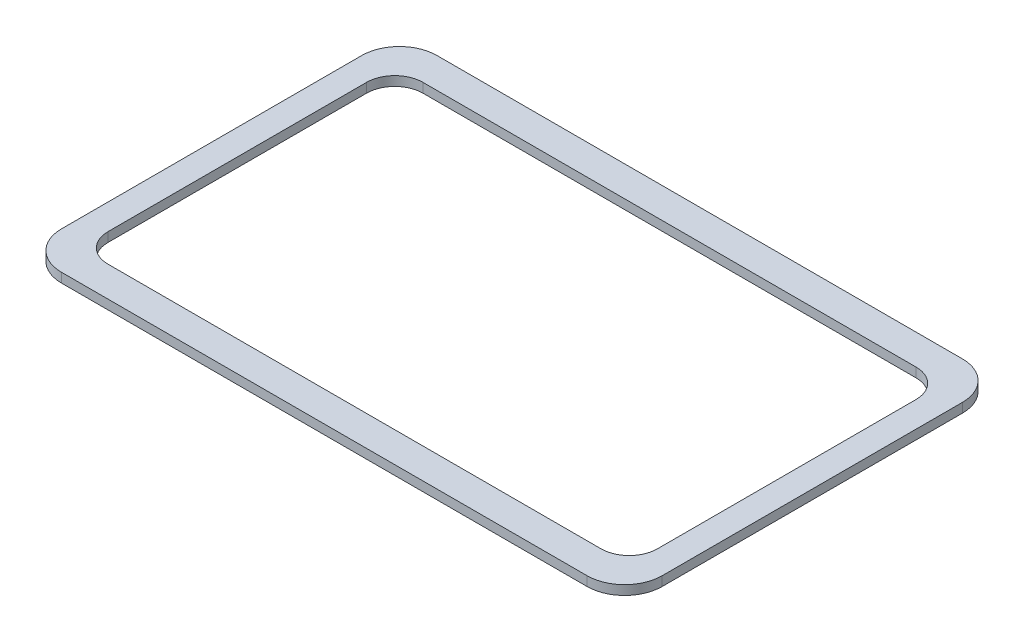
SolidWorks part; units mm, degrees
ref_plane "Front Plane" through (0, 0, 0) normal (0, 0, 1) x (1, 0, 0)
ref_plane "Top Plane" through (0, 0, 0) normal (0, 1, 0) x (1, 0, 0)
ref_plane "Right Plane" through (0, 0, 0) normal (1, 0, 0) x (0, 0, -1)
sketch "Sketch2" plane through (0, 49.3427, 0) normal (0, 1, 0) x (1, 0, 0)
  line L23 (74.7125, 86.6466) -> (-103.0875, 86.6466)
  line L24 (87.4125, -27.6534) -> (87.4125, 73.9466)
  line L25 (-97.5843, -30.1159) -> (69.2092, -30.1159)
  line L26 (-97.5843, -30.1159) -> (69.2092, -30.1159)
  line L32 (-103.0875, -40.3534) -> (74.7125, -40.3534) construction
  line L33 (-115.7875, 73.9466) -> (-115.7875, -27.6534) construction
  line L34 (-103.0875, -40.3534) -> (74.7125, -40.3534)
  line L35 (-115.7875, 73.9466) -> (-115.7875, -27.6534)
  line L66 (69.2092, 76.4092) -> (-97.5843, 76.4092)
  line L69 (69.2092, 76.4092) -> (-97.5843, 76.4092)
  line L104 (78.733, -20.5922) -> (78.733, 66.8854)
  line L107 (78.733, -20.5922) -> (78.733, 66.8854)
  line L119 (-107.108, 66.8854) -> (-107.108, 23.1466)
  line L120 (-107.108, 66.8854) -> (-107.108, 23.1466)
  line L121 (-107.108, 23.1466) -> (-107.108, -20.5922)
  line L122 (-107.108, 23.1466) -> (-107.108, -20.5922)
  arc A2 (87.4125, 73.9466) -> (74.7125, 86.6466) centre (74.7125, 73.9466) ccw
  arc A17 (-103.0875, 86.6466) -> (-115.7875, 73.9466) centre (-103.0875, 73.9466) ccw
  arc A21 (-107.108, -20.5922) -> (-97.5843, -30.1159) centre (-97.5843, -20.5922) ccw
  arc A25 (-107.108, -20.5922) -> (-97.5843, -30.1159) centre (-97.5843, -20.5922) ccw
  arc A29 (74.7125, -40.3534) -> (87.4125, -27.6534) centre (74.7125, -27.6534) ccw construction
  arc A30 (-115.7875, -27.6534) -> (-103.0875, -40.3534) centre (-103.0875, -27.6534) ccw construction
  arc A31 (74.7125, -40.3534) -> (87.4125, -27.6534) centre (74.7125, -27.6534) ccw
  arc A32 (-115.7875, -27.6534) -> (-103.0875, -40.3534) centre (-103.0875, -27.6534) ccw
  arc A49 (69.2092, -30.1159) -> (78.733, -20.5922) centre (69.2092, -20.5922) ccw
  arc A50 (69.2092, -30.1159) -> (78.733, -20.5922) centre (69.2092, -20.5922) ccw
  arc A51 (78.733, 66.8854) -> (69.2092, 76.4092) centre (69.2092, 66.8854) ccw
  arc A52 (78.733, 66.8854) -> (69.2092, 76.4092) centre (69.2092, 66.8854) ccw
  arc A53 (-97.5843, 76.4092) -> (-107.108, 66.8854) centre (-97.5843, 66.8854) ccw
  arc A54 (-97.5843, 76.4092) -> (-107.108, 66.8854) centre (-97.5843, 66.8854) ccw
  dimension "D1" = 1.5875
extrude "MainBody" add sketch "Sketch2" along normal blind 3.175
equation "\"ClampDepth\"= 3 / 8in"
equation "\"D1@Sketch2\"=0.0625"
